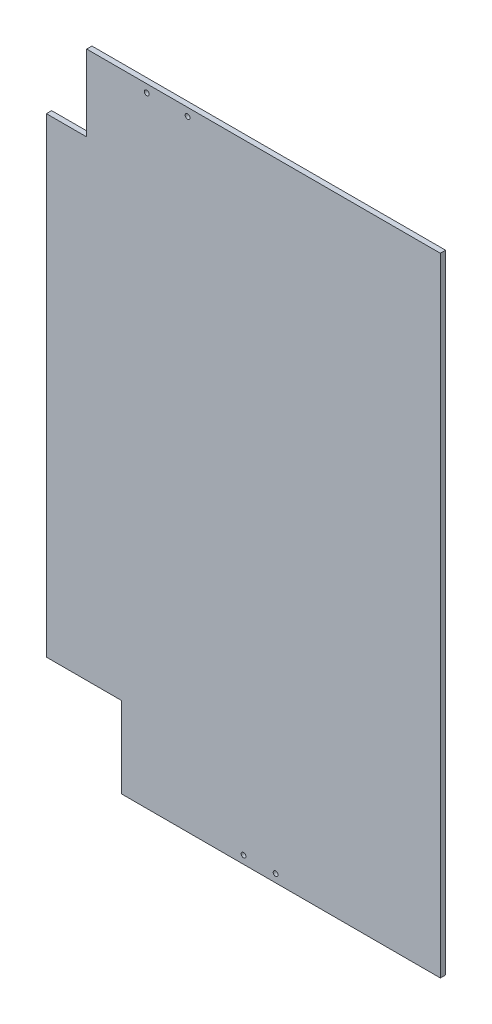
SolidWorks part; units mm, degrees
material "Balsa"
ref_plane "Front Plane" through (0, 0, 0) normal (0, 0, 1) x (1, 0, 0)
ref_plane "Top Plane" through (0, 0, 0) normal (0, 1, 0) x (1, 0, 0)
ref_plane "Right Plane" through (0, 0, 0) normal (1, 0, 0) x (0, 0, -1)
sketch "Sketch1" plane through (0, 0, 0) normal (0, 0, 1) x (1, 0, 0)
  line L0 (-5.7823, -13) -> (25.5, -13)
  line L2 (-5.7823, 1) -> (-5.7823, -13)
  line L5 (24.5, -14) -> (-24.5, -14) construction
  line L6 (272.4388, -265) -> (272.4388, 30)
  line L7 (-5.8246, -265) -> (65.6329, -265)
  line L8 (-5.8246, -265) -> (-5.8246, -225)
  line L11 (-5.8246, -265) -> (65.6329, -225) construction
  line L12 (-5.8246, -225) -> (65.6329, -265) construction
  line L15 (272.4388, -265) -> (25.5, -265)
  line L16 (25.5, 1) -> (25.5, -265)
  line L17 (-5.8246, -225) -> (25.5, -225)
  line L18 (-24.5, -224) -> (24.5, -224) construction
  line L19 (-5.7823, 1) -> (25.5, 1)
  line L20 (24.5, -224) -> (24.5, -14) construction
  line L21 (-85.1981, 31) -> (50.7481, 31) construction
  line L23 (25.5, 1) -> (25.5, 30)
  line L24 (25.5, 30) -> (272.4388, 30)
  line L28 (26.2777, -266) -> (-26.2882, -266) construction
  line L30 (-63.4467, 81) -> (255.5737, 81) construction
  line L31 (50.7481, 30) -> (272.4388, 30)
  line L32 (50.7481, 30) -> (50.7481, 77.7)
  line L33 (50.7481, 77.7) -> (272.4388, 77.7)
  line L34 (272.4388, 30) -> (272.4388, 77.7)
  line L35 (50.7481, 30) -> (272.4388, 77.7) construction
  line L36 (50.7481, 77.7) -> (272.4388, 30) construction
  line L37 (255.5737, -319) -> (-63.4467, -319) construction
  line L38 (272.4388, -265) -> (72.4388, -265)
  line L39 (272.4388, -265) -> (272.4388, -315.7)
  line L40 (272.4388, -315.7) -> (72.4388, -315.7)
  line L41 (72.4388, -265) -> (72.4388, -315.7)
  line L42 (272.4388, -265) -> (72.4388, -315.7) construction
  line L43 (272.4388, -315.7) -> (72.4388, -265) construction
  line L44 (50.7481, 31) -> (50.7481, -269) construction
  point P4 (32.4695, -6)
  point P10 (29.9042, -245)
  point P15 (48.1318, -132)
  point P24 (48.1318, 15.5)
  point P36 (161.5934, 53.85)
  point P42 (172.4388, -290.35)
  dimension "D1" = 1
  dimension "D2" = 1
  dimension "D3" = 1
  dimension "D4" = 1
  dimension "D5" = 1
  dimension "D6" = 31.3246
  dimension "D8" = 3.3
  dimension "D9" = 200
  dimension "D10" = 3.3
extrude "Boss-Extrude1" add sketch "Sketch1" along normal blind 3.3 contours L24 L23 L16 L7 L15 L6 | L19 L2 L0 L16 | L17 L8 L7 L16 | L24 L34 L33 L32 | L15 L41 L40 L39 region at (9.8589, -6, 0) region at (148.9694, -117.5, 0) region at (9.8377, -245, 0) region at (161.5934, 53.85, 0) region at (172.4388, -290.35, 0)
sketch "Sketch2" plane through (0, 0, 0) normal (0, 0, -1) x (-1, 0, 0)
  circle A0 centre (-113.9984, 72.7) radius 1.5
  circle A1 centre (-88.397, 72.7) radius 1.5
  circle A2 centre (-169.1689, -310.7) radius 1.5
  circle A3 centre (-149.0844, -310.7) radius 1.5
  dimension "D1" = 3
  dimension "D2" = 3
  dimension "D3" = 3
  dimension "D4" = 3
extrude "Cut-Extrude1" cut sketch "Sketch2" against normal through all
sketch "Sketch3" plane through (119.3915, 0, 256.0358) normal (0.4226, 0, 0.9063) x (0.9063, 0, -0.4226)
  line L1 (293.4595, -146) -> (268.9595, -146)
  line L2 (293.4595, -146) -> (293.4595, -92)
  line L3 (293.4595, -92) -> (268.9595, -92)
  line L4 (268.9595, -146) -> (268.9595, -92)
  line L5 (293.4595, -146) -> (268.9595, -92) construction
  line L6 (293.4595, -92) -> (268.9595, -146) construction
  point P4 (281.2095, -119)
sketch "Sketch4" plane through (0, 0, 0) normal (0, 0, -1) x (-1, 0, 0)
  line L1 (-272.4388, -92) -> (-242.4388, -92)
  line L2 (-272.4388, -92) -> (-272.4388, -146)
  line L3 (-272.4388, -146) -> (-242.4388, -146)
  line L4 (-242.4388, -92) -> (-242.4388, -146)
  line L5 (-272.4388, -92) -> (-242.4388, -146) construction
  line L6 (-272.4388, -146) -> (-242.4388, -92) construction
  line L7 (-272.4388, -315.7) -> (-272.4388, 77.7) construction
  point P4 (-257.4388, -119)
  dimension "D1" = 54
  dimension "D2" = 30
sketch "Sketch5" plane through (0, 0, 0) normal (0, 0, -1) x (-1, 0, 0)
  line L0 (5.7823, 1) -> (-25.5, 1) construction
  line L1 (5.8246, -265) -> (-25.5, -265)
  line L2 (5.8246, -265) -> (5.8246, 1)
  line L3 (5.8246, 1) -> (-25.5, 1)
  line L4 (-25.5, -265) -> (-25.5, 1)
  line L5 (5.8246, -265) -> (-25.5, 1) construction
  line L6 (5.8246, 1) -> (-25.5, -265) construction
  line L7 (-25.5, 1) -> (-25.5, 30) construction
  point P4 (-9.8377, -132)
extrude "Cut-Extrude4" cut sketch "Sketch5" against normal blind 10
